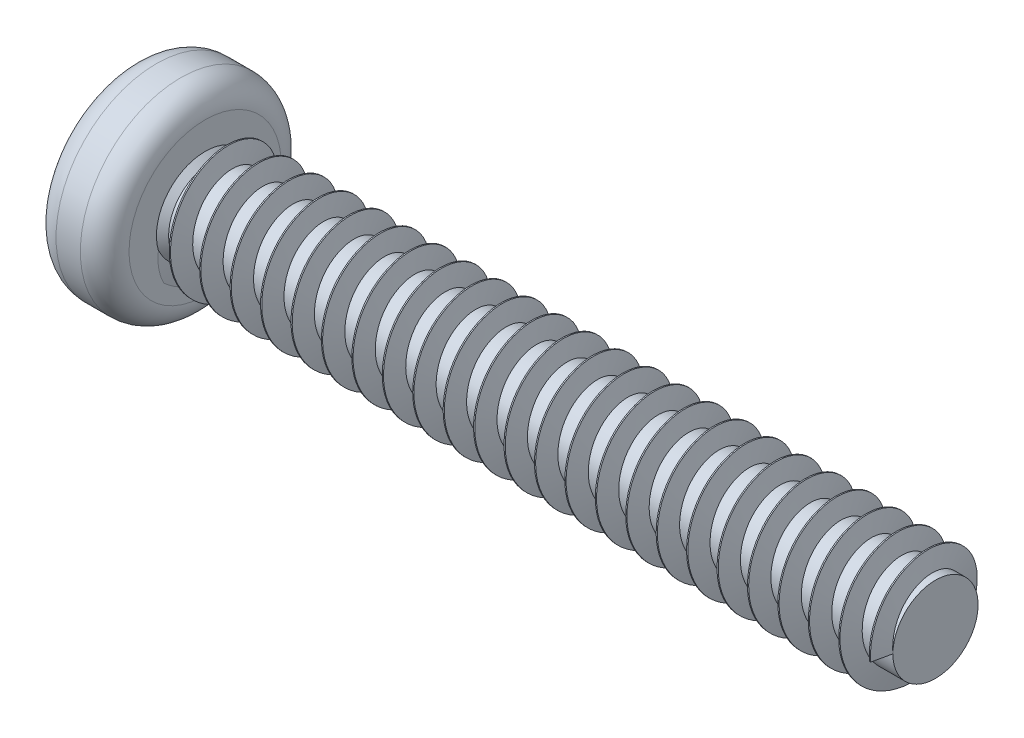
SolidWorks part; units mm, degrees
ref_plane "Front Plane" through (0, 0, 0) normal (0, 0, 1) x (1, 0, 0)
ref_plane "Top Plane" through (0, 0, 0) normal (0, 1, 0) x (1, 0, 0)
ref_plane "Right Plane" through (0, 0, 0) normal (1, 0, 0) x (0, 0, -1)
sketch "Sketch1" plane through (0, 0, 0) normal (0, 0, 1) x (1, 0, 0)
  line L0 (0, 0) -> (0, 1.25)
  line L1 (0.4, 1.65) -> (0.8, 1.65)
  line L2 (1.2, 1.25) -> (1.2, 0.8)
  line L3 (1.3, 0.7) -> (13.2, 0.7)
  line L4 (13.2, 0.7) -> (13.2, 0)
  line L5 (13.2, 0) -> (0, 0) construction
  line L6 (1.2, 0.8) -> (1.3, 0.7)
  line L7 (0, 0) -> (13.2, 0)
  arc A0 (0.8, 1.65) -> (1.2, 1.25) centre (0.8, 1.25) cw
  arc A1 (0, 1.25) -> (0.4, 1.65) centre (0.4, 1.25) cw
  point P5 (1.2, 0.7)
  point P9 (1.2, 1.65)
  point P12 (0, 1.65)
  dimension "D3" = 0.4
  dimension "D1" = 3.3
  dimension "D2" = 1.2
  dimension "D4" = 1.4
  dimension "ScrewLenght" = 12
revolve "Revolve1" add sketch "Sketch1" angle 360 about L5
sketch "Sketch2" plane through (0, 0, 0) normal (-1, 0, 0) x (0, 0, 1)
  line L1 (0.2, -0.85) -> (-0.2, -0.85)
  line L2 (0.2, -0.85) -> (0.2, 0.85)
  line L3 (0.2, 0.85) -> (-0.2, 0.85)
  line L4 (-0.2, -0.85) -> (-0.2, 0.85)
  line L5 (0.2, -0.85) -> (-0.2, 0.85) construction
  line L6 (0.2, 0.85) -> (-0.2, -0.85) construction
  line L7 (0.85, 0.2) -> (-0.85, 0.2)
  line L8 (0.85, 0.2) -> (0.85, -0.2)
  line L9 (0.85, -0.2) -> (-0.85, -0.2)
  line L10 (-0.85, 0.2) -> (-0.85, -0.2)
  line L11 (0.85, 0.2) -> (-0.85, -0.2) construction
  line L12 (0.85, -0.2) -> (-0.85, 0.2) construction
  point P0 (0, 0)
  point P6 (0, 0)
  dimension "D1" = 0.4
  dimension "D2" = 1.7
extrude "Cut-Extrude1" cut sketch "Sketch2" against normal blind 0.8 draft 9 contours L2 L9 L4 L1 | L7 L10 L9 L4 | L9 L2 L7 L4 | L7 L2 L3 L4 | L9 L8 L7 L2 region at (0, -0.525, 0) region at (0, 0, 0) region at (0, 0, 0.525) region at (0, 0, -0.525) region at (0, 0.525, 0)
thread "Thread3" pitch 0.3 method extrude profile "Thread Profile4" start angle 0, offset 0, length 0, pitch 0.5, diameter 1.4
ref_plane "Plane4" through (13.2, 0, 0.7) normal (0, -1, 0) x (0, 0, 1)
sketch "Thread Profile4" plane through (13.2, 0, 0.7) normal (0, -1, 0) x (0, 0, 1)
  line L0 (0, 0) -> (0, 0.3) construction
  line L1 (0, 0) -> (0.3, 0.0665)
  line L2 (0.3, 0.0665) -> (0.3, 0.0865)
  line L3 (0.3, 0.0865) -> (0, 0.153)
  line L4 (0.3, 0.0765) -> (0, 0.0765) construction
  line L11 (0, 0) -> (0, 0.153)
  point P2 (0, 0)
  dimension "Pitch" = 0.3
  dimension "Profile_Angle" = 25
  dimension "Profile_Land" = 0.02
  dimension "Profile_Height" = 0.3
